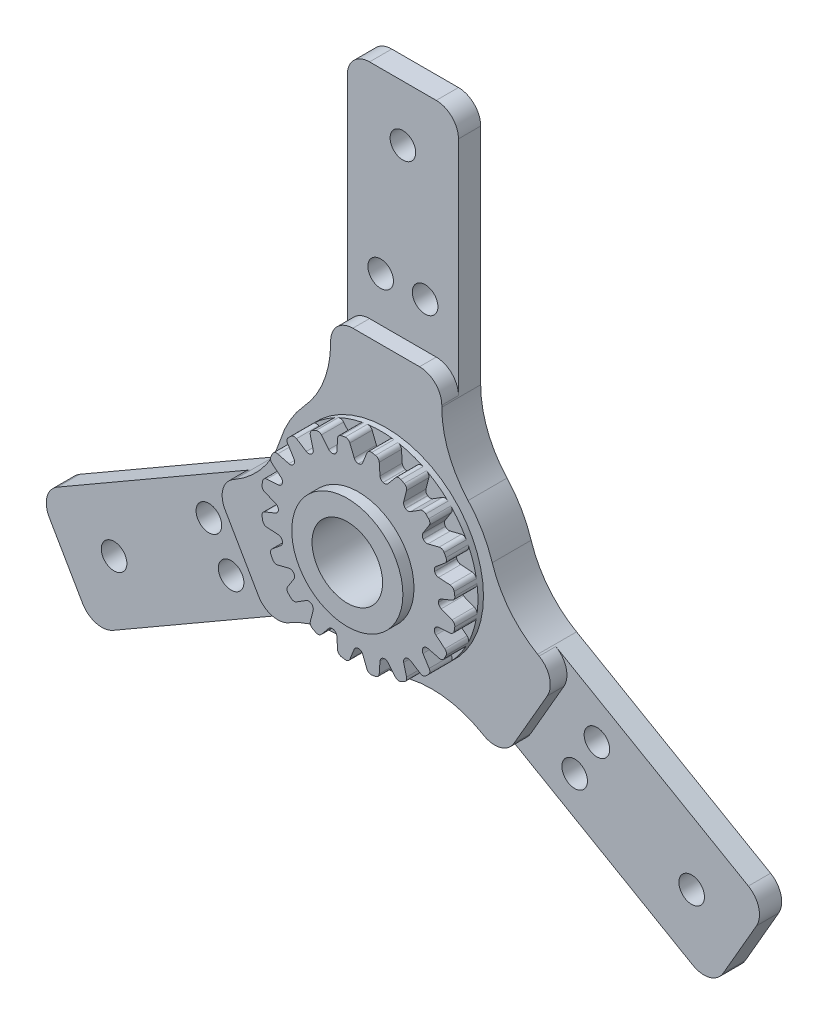
SolidWorks part; units mm, degrees
note: '?' marks a value the reader was unsure of.
ref_plane "Front Plane" through (0, 0, 0) normal (0, 0, 1) x (1, 0, 0)
ref_plane "Top Plane" through (0, 0, 0) normal (0, 1, 0) x (1, 0, 0)
ref_plane "Right Plane" through (0, 0, 0) normal (1, 0, 0) x (0, 0, -1)
sketch "Sketch2" plane through (0, 0, 0) normal (0, 0, 1) x (1, 0, 0)
  circle A0 centre (0, 0) radius 20
extrude "Extrude2" add sketch "Sketch2" along normal blind 7
sketch "Sketch3" plane through (0, 0, 7) normal (0, 0, 1) x (1, 0, 0)
  circle A0 centre (0, 0) radius 17.5
extrude "Extrude3" add sketch "Sketch3" along normal blind 5
sketch "Sketch4" plane through (0, 0, 12) normal (0, 0, 1) x (1, 0, 0)
  circle A0 centre (0, 0) radius 10
extrude "Extrude4" add sketch "Sketch4" along normal blind 2
sketch "Sketch5" plane through (0, 0, 0) normal (0, 0, 1) x (1, 0, 0)
  line L1 (-10, 70) -> (10, 70)
  line L2 (-10, 70) -> (-10, 1)
  line L3 (-10, 1) -> (10, 1)
  line L4 (10, 70) -> (10, 1)
extrude "Extrude5" add sketch "Sketch5" along normal blind 7
ref_axis "Axis1" through (0, 0, 14) along (0, 0, -1)?
pattern_circular "CirPattern3" count 3 over 360 about axis through (0, 0, 0) along (0, 0, 1) of "Extrude5"
fillet "Fillet1" radius 18 6 edges at (-20, 0, 3.5) (-10, 17.3205, 3.5) (10, 17.3205, 3.5) (20, 0, 3.5) (10, -17.3205, 3.5) (-10, -17.3205, 3.5)
sketch "Sketch6" plane through (0, 0, 0) normal (0, 0, 1) x (1, 0, 0)
  line L1 (-15, 75) -> (15, 75)
  line L2 (-15, 75) -> (-15, 30)
  line L3 (-15, 30) -> (15, 30)
  line L4 (15, 75) -> (15, 30)
extrude "Cut-Extrude1" cut sketch "Sketch6" along normal blind 7 from offset 4
pattern_circular "CirPattern4" count 3 over 360 about axis through (0, 0, 0) along (0, 0, 1) of "Cut-Extrude1"
fillet "Fillet2" radius 4 6 edges at (20.9808, -23.6603, 5.5) (30.9808, -6.3397, 5.5) (-30.9808, -6.3397, 5.5) (-20.9808, -23.6603, 5.5) (-10, 30, 5.5) (10, 30, 5.5)
fillet "Fillet3" radius 4 6 edges at (-55.6218, -43.6603, 2) (-65.6218, -26.3397, 2) (-10, 70, 2) (10, 70, 2) (55.6218, -43.6603, 2) (65.6218, -26.3397, 2)
sketch "Sketch7" plane through (0, 0, 0) normal (0, 0, 1) x (1, 0, 0)
  circle A0 centre (4, 38) radius 2.3
  circle A1 centre (-4, 38) radius 2.3
  circle A2 centre (0, 60) radius 2.3
extrude "Cut-Extrude3" cut sketch "Sketch7" along normal blind 7
pattern_circular "CirPattern5" count 3 over 360 about axis through (0, 0, 0) along (0, 0, 1) of "Cut-Extrude3"
sketch "Sketch9" plane through (0, 0, 14) normal (0, 0, 1) x (1, 0, 0)
  circle A0 centre (0, 0) radius 6.35
extrude "Cut-Extrude4" cut sketch "Sketch9" against normal blind 16
sketch "Sketch10" plane through (0, 0, 12) normal (0, 0, 1) x (1, 0, 0)
  line L0 (-2, 18) -> (2, 18)
  line L1 (2, 18) -> (0.5619, 14.404)
  line L2 (-2, 18) -> (-0.5619, 14.404)
  line L3 (0.5619, 14.404) -> (-0.5619, 14.404)
extrude "Cut-Extrude5" cut sketch "Sketch10" against normal blind 4
pattern_circular "CirPattern6" count 20 over 360 about axis through (0, 0, 0) along (0, 0, 1) of "Cut-Extrude5"
fillet "Fillet4" radius 0.8 80 edges at (1.7644, 17.4108, 10) (0.5619, 14.404, 10) (-0.5619, 14.404, 10) (-1.7644, 17.4108, 10) (11.3228, -8.9211, 10) (11.9834, -8.0119, 10) (13.5254, -4.9855, 10) (13.8727, -3.9167, 10) (14.404, -0.5619, 10) (14.404, 0.5619, 10) (13.8727, 3.9167, 10) (13.5254, 4.9855, 10) (11.9834, 8.0119, 10) (11.3228, 8.9211, 10) (8.9211, 11.3228, 10) (8.0119, 11.9834, 10) (4.9855, 13.5254, 10) (3.9167, 13.8727, 10) (-3.9167, 13.8727, 10) (-4.9855, 13.5254, 10) (-8.0119, 11.9834, 10) (-8.9211, 11.3228, 10) (-11.3228, 8.9211, 10) (-11.9834, 8.0119, 10) (-13.5254, 4.9855, 10) (-13.8727, 3.9167, 10) (-17.4108, 1.7644, 10) (-14.404, 0.5619, 10) (-14.404, -0.5619, 10) (-17.4108, -1.7644, 10) (-17.1039, -3.7022, 10) (-13.8727, -3.9167, 10) (-13.5254, -4.9855, 10) (-16.0135, -7.0583, 10) (-15.1227, -8.8064, 10) (-11.9834, -8.0119, 10) (-11.3228, -8.9211, 10) (-13.0486, -11.6612, 10) (-11.6612, -13.0486, 10) (-8.9211, -11.3228, 10) (-8.0119, -11.9834, 10) (-8.8064, -15.1227, 10) (-7.0583, -16.0135, 10) (-4.9855, -13.5254, 10) (-3.9167, -13.8727, 10) (-3.7022, -17.1039, 10) (-1.7644, -17.4108, 10) (-0.5619, -14.404, 10) (0.5619, -14.404, 10) (1.7644, -17.4108, 10) (3.7022, -17.1039, 10) (3.9167, -13.8727, 10) (4.9855, -13.5254, 10) (8.0119, -11.9834, 10) (8.9211, -11.3228, 10) (7.0583, -16.0135, 10) (8.8064, -15.1227, 10) (11.6612, -13.0486, 10) (13.0486, -11.6612, 10) (15.1227, -8.8064, 10) (16.0135, -7.0583, 10) (17.1039, -3.7022, 10) (17.4108, -1.7644, 10) (17.4108, 1.7644, 10) (17.1039, 3.7022, 10) (16.0135, 7.0583, 10) (15.1227, 8.8064, 10) (-17.1039, 3.7022, 10) (-16.0135, 7.0583, 10) (-15.1227, 8.8064, 10) (-13.0486, 11.6612, 10) (-11.6612, 13.0486, 10) (-8.8064, 15.1227, 10) (-7.0583, 16.0135, 10) (-3.7022, 17.1039, 10) (3.7022, 17.1039, 10) (7.0583, 16.0135, 10) (8.8064, 15.1227, 10) (13.0486, 11.6612, 10) (11.6612, 13.0486, 10)
